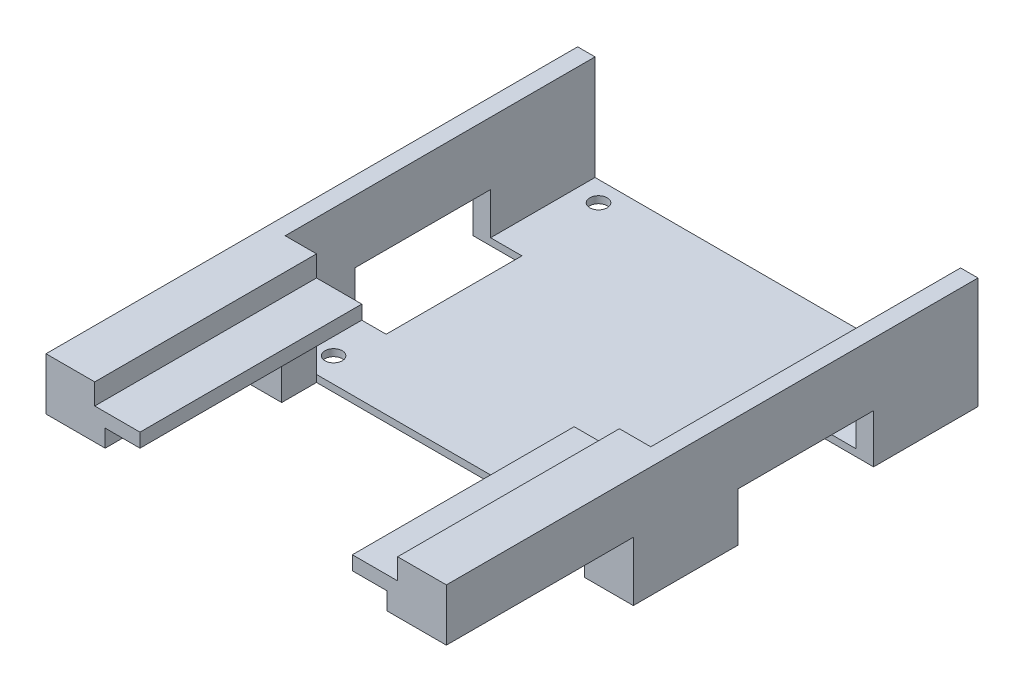
SolidWorks part; units mm, degrees
ref_plane "Front Plane" through (0, 0, 0) normal (0, 0, 1) x (1, 0, 0)
ref_plane "Top Plane" through (0, 0, 0) normal (0, 1, 0) x (1, 0, 0)
ref_plane "Right Plane" through (0, 0, 0) normal (1, 0, 0) x (0, 0, -1)
sketch "Sketch1" plane through (0, 0, 0) normal (0, 1, 0) x (1, 0, 0)
  line L0 (0, 0) -> (0, 76.35) construction
  line L1 (-28.75, 76.35) -> (28.75, 76.35)
  line L2 (28.75, 76.35) -> (28.75, 0)
  line L3 (28.75, 0) -> (21.75, 0)
  line L4 (21.75, 0) -> (21.75, 31.85)
  line L5 (21.75, 31.85) -> (-21.75, 31.85)
  line L6 (-21.75, 31.85) -> (-21.75, 0)
  line L7 (-21.75, 0) -> (-28.75, 0)
  line L8 (-28.75, 0) -> (-28.75, 76.35)
  line L9 (-26.25, 76.35) -> (-26.25, 31.85)
  line L14 (-26.25, 31.85) -> (-21.75, 31.85)
  line L15 (26.25, 76.35) -> (26.25, 31.85)
  line L16 (26.25, 31.85) -> (21.75, 31.85)
  line L17 (28.75, 74.35) -> (30.25, 74.35)
  line L18 (-28.75, 41.35) -> (-26.25, 41.35)
  line L19 (-28.75, 41.35) -> (-28.75, 53.35)
  line L20 (-28.75, 53.35) -> (-26.25, 53.35)
  line L21 (-26.25, 41.35) -> (-26.25, 53.35)
  line L22 (30.25, 68.35) -> (28.75, 68.35)
  line L23 (-30.25, 68.35) -> (-28.75, 68.35)
  line L24 (-28.75, 74.35) -> (-30.25, 74.35)
  arc A0 (30.25, 68.35) -> (30.25, 74.35) centre (30.25, 71.35) ccw
  arc A1 (-30.25, 68.35) -> (-30.25, 74.35) centre (-30.25, 71.35) cw
  point P10 (0, 76.35)
  point P16 (-27.5, 41.35)
  point P17 (-22.85, 73.45)
  point P18 (22.85, 73.45)
  point P23 (22.85, 35.4)
  point P24 (-22.85, 35.4)
  point P25 (23.5, 3)
  point P26 (26, 29.35)
  point P27 (-26, 29.35)
  point P28 (-23.5, 3)
  point P40 (30.25, 71.35)
  point P41 (-30.25, 71.35)
  dimension "D16" = 3
  dimension "D1" = 2.5
  dimension "D2" = 7
  dimension "D3" = 43.5
  dimension "D4" = 31.85
  dimension "D5" = 44.5
  dimension "D6" = 23
  dimension "D7" = 12
  dimension "D8" = 22.85
  dimension "D9" = 38.05
  dimension "D10" = 2.9
  dimension "D11" = 47
  dimension "D12" = 52
  dimension "D13" = 47
  dimension "D14" = 3
  dimension "D15" = 1.5
  dimension "D17" = 2
extrude "Boss-Extrude1" add sketch "Sketch1" along normal blind 1 contours L5 L0 L1 L9 L14 | L0 L5 L16 L15 L1 region at (-13.125, 0, -54.1) region at (13.125, 0, -54.1)
extrude "Boss-Extrude2" add sketch "Sketch1<3>" along normal blind 16 contours L18 L8 L7 L6 L14 L9 | L8 L20 L9 L1 | L15 L16 L4 L3 L2 L1 | L20 L8 L18 L9 region at (-27.5, 0, -64.85) region at (25.999, 0, -28.6329) region at (-27.5, 0, -47.35) region at (-25.4666, 0, -17.9154)
sketch "Sketch1<3>" plane through (0, 0, 0) normal (0, 1, 0) x (1, 0, 0) same geometry as "Sketch1"
hole_wizard "Ø2.5 (2.5) Diameter Hole1" positions "Sketch4" profile "Sketch5" hole size "Ø2.5" standard "ANSI Metric"
sketch "Sketch4" plane through (0, 0, 0) normal (0, -1, 0) x (-1, 0, 0)
  point P0 (-22.85, 73.45)
  point P3 (22.85, 73.45)
  point P6 (26, 29.35)
  point P9 (22.85, 35.4)
  point P12 (-22.85, 35.4)
  point P15 (-26, 29.35)
  point P18 (-23.5, 3)
  point P21 (23.5, 3)
  point P24 (-30.25, 71.35)
  point P27 (30.25, 71.35)
sketch "Sketch5" plane through (22.85, 0, -73.45) normal (1, 0, 0) x (0, 0, -1)
  line L0 (0, 0) -> (0, 12.7511)
  line L1 (0, 12.7511) -> (1.25, 12)
  line L2 (1.25, 12) -> (1.25, 0)
  line L5 (1.25, 0) -> (0, 0)
  line L10 (0, 12.7511) -> (-1.25, 12) construction
  line L11 (0, -6.35) -> (0, 107.95) construction
  dimension "Hole Dia." = 2.5
  dimension "Hole Depth" = 12
  dimension "Drill Angle" = 118
sketch "Sketch6" plane through (0, 0, 0) normal (0, 0, 1) x (1, 0, 0)
  line L0 (-21.75, 16) -> (-21.75, 0) construction
  line L5 (0, -1.6497) -> (0, 21.9352) construction
  line L6 (-21.75, 11) -> (-15.25, 11)
  line L7 (-21.75, 11) -> (-21.75, 13)
  line L8 (-21.75, 13) -> (-15.25, 13)
  line L9 (-15.25, 11) -> (-15.25, 13)
  line L10 (-28.75, 16) -> (-28.75, 0) construction
  line L11 (-20.25, 11) -> (-21.75, 11)
  line L12 (-20.25, 11) -> (-20.25, 8.5)
  line L13 (-20.25, 8.5) -> (-21.75, 8.5)
  line L14 (-21.75, 11) -> (-21.75, 8.5)
  line L15 (-21.75, 0) -> (-28.75, 0)
  line L16 (-21.75, 0) -> (-21.75, 8.5)
  line L17 (-21.75, 8.5) -> (-28.75, 8.5)
  line L18 (-28.75, 0) -> (-28.75, 8.5)
  line L19 (28.75, 0) -> (28.75, 8.5)
  line L20 (21.75, 8.5) -> (28.75, 8.5)
  line L21 (21.75, 0) -> (21.75, 8.5)
  line L22 (21.75, 0) -> (28.75, 0)
  line L23 (21.75, 11) -> (21.75, 8.5)
  line L24 (20.25, 8.5) -> (21.75, 8.5)
  line L25 (20.25, 11) -> (20.25, 8.5)
  line L26 (20.25, 11) -> (21.75, 11)
  line L27 (15.25, 11) -> (15.25, 13)
  line L28 (21.75, 13) -> (15.25, 13)
  line L29 (21.75, 11) -> (21.75, 13)
  line L30 (21.75, 11) -> (15.25, 11)
  line L31 (-21.75, 16) -> (-28.75, 16) construction
  line M21 (21.75, 0) -> (28.75, 0)
  line M22 (28.75, 0) -> (28.75, 16)
  line M24 (21.75, 16) -> (21.75, 0)
  dimension "D1" = 6.5
  dimension "D2" = 3
  dimension "D3" = 2
  dimension "D4" = 2.5
  dimension "D5" = 1.5
extrude "Boss-Extrude3" add sketch "Sketch6" against normal up to surface (31.85 mm away) contours L30 L26 L28 L27 M24 | L26 L25 L24 M24 | L6 L9 L8 L7 | L6 L14 L13 L12 region at (-18.5, 12, 0) region at (-21, 9.75, 0) region at (21, 9.75, 0) region at (18.5, 12, 0) up to face at (0, 0.5, -31.85)
extrude "Cut-Extrude1" cut sketch "Sketch6<4>" against normal blind 26.85 contours L18 L15 L16 L17 | L20 M24 M21 M22 region at (-25.25, 4.25, 0) region at (25.25, 4.25, 0)
sketch "Sketch6<4>" plane through (0, 0, 0) normal (0, 0, 1) x (1, 0, 0) same geometry as "Sketch6"
sketch "Sketch8" plane through (0, 0, 0) normal (0, -1, 0) x (1, 0, 0)
  line L0 (0, 17.5937) -> (0, -89.2896) construction
  line L1 (-28.75, -61.35) -> (-21.75, -61.35)
  line L2 (-28.75, -61.35) -> (-28.75, -41.85)
  line L3 (-28.75, -41.85) -> (-21.75, -41.85)
  line L4 (-21.75, -61.35) -> (-21.75, -41.85)
  line L6 (-28.75, -76.35) -> (28.75, -76.35) construction
  line L8 (21.75, -61.35) -> (21.75, -41.85)
  line L9 (28.75, -41.85) -> (21.75, -41.85)
  line L10 (28.75, -61.35) -> (28.75, -41.85)
  line L11 (28.75, -61.35) -> (21.75, -61.35)
  line L12 (-28.75, -26.85) -> (-28.75, -76.35) construction
  point P9 (0, 0)
  point P16 (0, 0)
  dimension "D1" = 15
  dimension "D2" = 7
  dimension "D3" = 19.5
extrude "Cut-Extrude2" cut sketch "Sketch8" against normal blind 7
